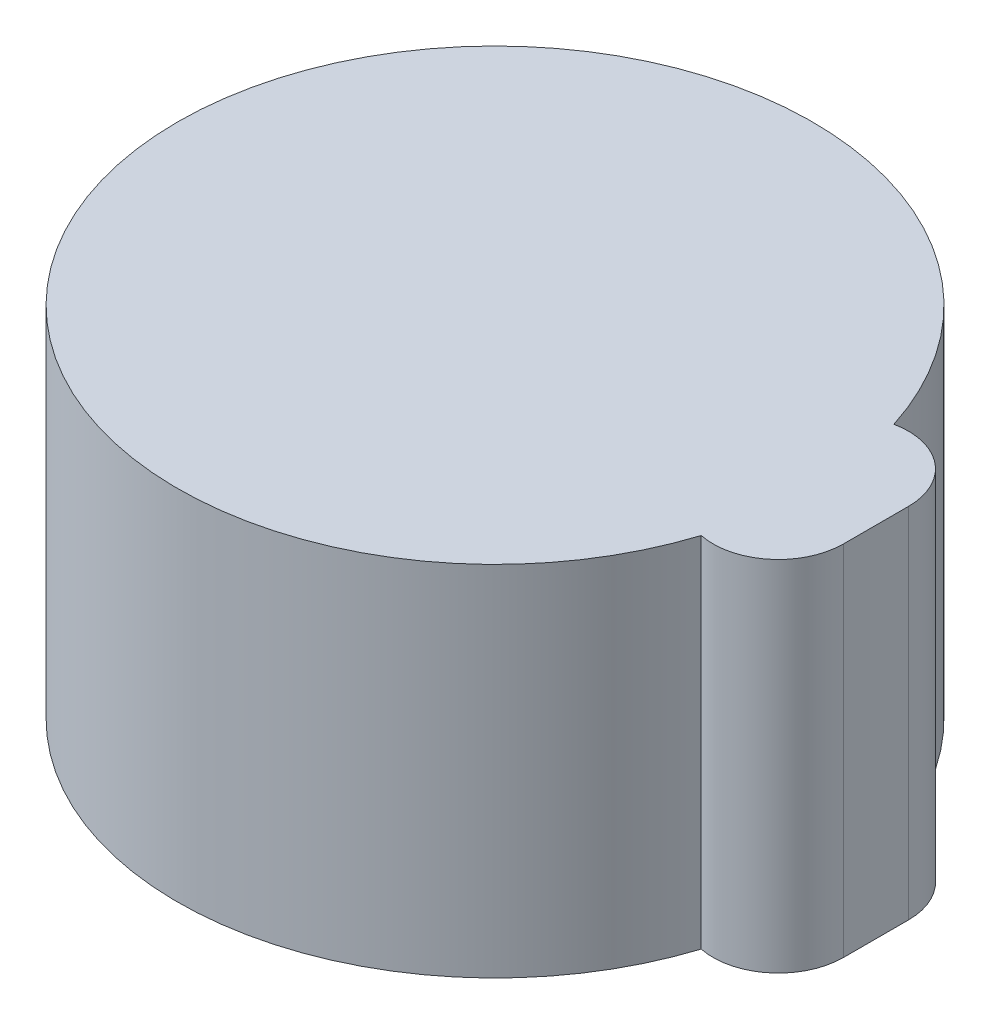
SolidWorks part; units mm, degrees
ref_plane "Front Plane" through (0, 0, 0) normal (0, 0, 1) x (1, 0, 0)
ref_plane "Top Plane" through (0, 0, 0) normal (0, 1, 0) x (1, 0, 0)
ref_plane "Right Plane" through (0, 0, 0) normal (1, 0, 0) x (0, 0, -1)
sketch "Sketch1" plane through (0, 0, 0) normal (0, 1, 0) x (1, 0, 0)
  line L0 (-6.6188, 0) -> (7.2814, 0) construction
  line L1 (5.3493, 0.5) -> (5.8493, 0.5) construction
  line L2 (0, 4.375) -> (0, 4.875) construction
  line L3 (5.8493, 0.5) -> (5.8493, -0.5)
  line L4 (4.7726, 0.9941) -> (4.2606, 0.9941)
  line L5 (4.7726, -0.9941) -> (4.2606, -0.9941)
  line L6 (5.3493, 0.5) -> (5.3493, -0.5)
  circle A0 centre (0, 0) radius 4.375
  circle A1 centre (0, 0) radius 4.875
  circle A2 centre (4.8493, 0.5) radius 0.5
  circle A3 centre (4.8493, -0.5) radius 0.5
  circle A4 centre (4.8493, 0.5) radius 1
  circle A5 centre (4.8493, -0.5) radius 1
  dimension "D1" = 8.75
  dimension "D2" = 0.5
  dimension "D3" = 1
extrude "Boss-Extrude1" add sketch "Sketch1" along normal blind 5 contours A5 A0 A4 A1 | A1 A4 A0 A2 | A5 A4 A1 A2 L6 | A4 A5 L6 | A5 L3 A4 | A5 A4 L6 A3 A1 | A0 A5 A1 A3 region at (5.3492, 0, -0.8965) region at (5.8096, 0, 0) region at (5.3492, 0, 0.8965) region at (4.3432, 0, -1.5174) region at (4.4904, 0, -1.197) region at (5.4819, 0, 0) region at (4.4904, 0, 1.197)
sketch "Sketch3" plane through (0, 5, 0) normal (0, 1, 0) x (1, 0, 0)
  line L1 (5.8493, -0.5) -> (5.8493, 0.5)
  line L2 (5.8493, -0.5) -> (5.8493, 0.5)
  arc A3 (4.6452, -1.479) -> (5.8493, -0.5) centre (4.8493, -0.5) ccw
  arc A4 (5.8493, 0.5) -> (4.6452, 1.479) centre (4.8493, 0.5) ccw
  arc A5 (4.6452, 1.479) -> (4.6452, -1.479) centre (0, 0) ccw
  arc A6 (4.6452, -1.479) -> (5.8493, -0.5) centre (4.8493, -0.5) ccw
  arc A7 (5.8493, 0.5) -> (4.6452, 1.479) centre (4.8493, 0.5) ccw
  arc A8 (4.6452, 1.479) -> (4.6452, -1.479) centre (0, 0) ccw
  dimension "D1" = 0
extrude "Boss-Extrude2" add sketch "Sketch3" along normal blind 0.5
sketch "Sketch4" plane through (0, 5, 0) normal (0, -1, 0) x (1, 0, 0)
  line L0 (4.2606, 0.9941) -> (3.7453, 0.9941)
  line L1 (4.2606, -0.9941) -> (3.7453, -0.9941)
  circle A0 centre (0, 0) radius 3.875
  arc A1 (4.2606, 0.9941) -> (4.2606, -0.9941) centre (0, 0) ccw construction
  arc M6 (4.2606, 0.9941) -> (4.2606, -0.9941) centre (0, 0) ccw
  dimension "D1" = 0.5
extrude "Boss-Extrude3" add sketch "Sketch4" along normal blind 1 contours A0 M6 region at (4.0029, 5, 1.117)
sketch "Sketch5" plane through (0, 4, 0) normal (0, -1, 0) x (1, 0, 0)
  line L0 (0, 4.375) -> (0, -4.375) construction
  line L1 (3.0936, -3.0936) -> (-3.0936, 3.0936) construction
  line L2 (-3.0936, -3.0936) -> (3.0936, 3.0936) construction
  arc A0 (4.2606, 0.9941) -> (4.2606, -0.9941) centre (0, 0) ccw construction
  arc A1 (4.2606, 0.9941) -> (4.2606, -0.9941) centre (0, 0) ccw construction
  circle A2 centre (3.0936, 3.0936) radius 0.25
  circle A3 centre (-3.0936, 3.0936) radius 0.25
  circle A4 centre (-3.0936, -3.0936) radius 0.25
  circle A5 centre (3.0936, -3.0936) radius 0.25
  dimension "D2" = 0.5
  dimension "D1" = 45
extrude "Boss-Extrude4" add sketch "Sketch5" along normal up to surface (4 mm away) up to face at (2.9836, 0, 0)
